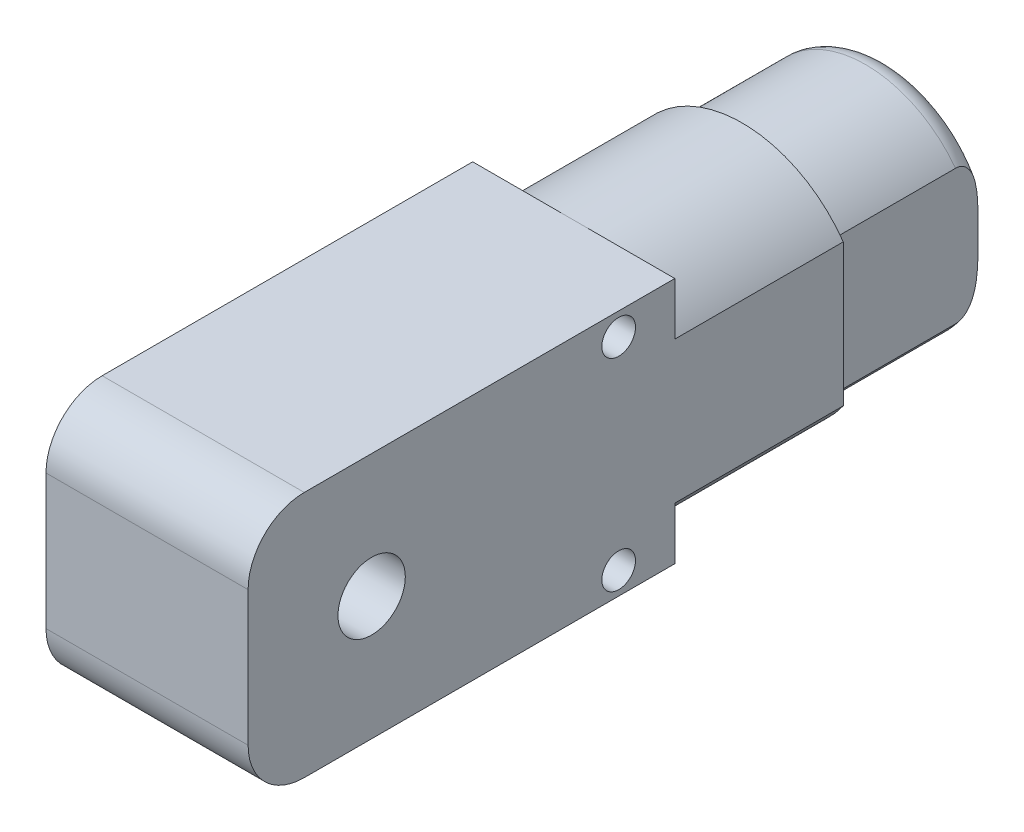
SolidWorks part; units mm, degrees
ref_plane "Front Plane" through (0, 0, 0) normal (0, 0, 1) x (1, 0, 0)
ref_plane "Top Plane" through (0, 0, 0) normal (0, 1, 0) x (1, 0, 0)
ref_plane "Right Plane" through (0, 0, 0) normal (1, 0, 0) x (0, 0, -1)
sketch "Sketch1" plane through (0, 0, 0) normal (1, 0, 0) x (0, 0, -1)
  line L7 (19, -11) -> (-19, -11)
  line L8 (19, -11) -> (19, 11)
  line L9 (19, 11) -> (-19, 11)
  line L10 (-19, -11) -> (-19, 11)
  line L11 (19, -11) -> (-19, 11) construction
  line L12 (19, 11) -> (-19, -11) construction
  point P0 (0, 0)
  dimension "D1" = 22
  dimension "D2" = 38
extrude "Boss-Extrude1" add sketch "Sketch1" along normal blind 18
fillet "Fillet1" radius 5 2 edges at (9, 11, 19) (9, -11, 19)
sketch "Sketch3" plane through (0, 0, -19) normal (0, 0, -1) x (-1, 0, 0)
  line L0 (9.9, 0) -> (-9.9, 0) construction
  line L1 (-18, 6.3246) -> (-18, -6.3246)
  line L3 (0, -6.3246) -> (0, 6.3246)
  arc A0 (-18, -6.3246) -> (0, -6.3246) centre (-9, 0) ccw
  arc A1 (0, 6.3246) -> (-18, 6.3246) centre (-9, 0) ccw
extrude "Boss-Extrude2" add sketch "Sketch3" along normal blind 15
sketch "Sketch4" plane through (0, 0, -34) normal (0, 0, -1) x (-1, 0, 0)
  line L0 (-17, 6) -> (-17, -6)
  line L1 (-18, 6.3246) -> (-18, -6.3246) construction
  line L2 (-1, -6) -> (-1, 6)
  line L3 (0, 12.1) -> (0, -12.1) construction
  arc A0 (-17, -6) -> (-1, -6) centre (-9, 0) ccw
  arc A1 (-1, 6) -> (-17, 6) centre (-9, 0) ccw
  dimension "D1" = 1
  dimension "D2" = 1
extrude "Boss-Extrude3" add sketch "Sketch4" along normal blind 13
fillet "Fillet2" radius 2 2 edges at (9, 10, -47) (9, -10, -47)
sketch "Sketch5" plane through (18, 0, 0) normal (1, 0, 0) x (0, 0, -1)
  line L0 (9.9, 0) -> (-9.9, 0) construction
  line L1 (-19, 6) -> (-19, -6) construction
  line L3 (19, -11) -> (19, -6.3246) construction
  line L4 (-14, -11) -> (19, -11) construction
  circle A0 centre (-8, 0) radius 3
  circle A1 centre (14, -9) radius 1.5
  circle A2 centre (14, 9) radius 1.5
  dimension "D1" = 11
  dimension "D2" = 6
  dimension "D3" = 5
  dimension "D5" = 3
  dimension "D4" = 2
extrude "Cut-Extrude1" cut sketch "Sketch5" against normal through all contours A0 | A2 | A1
